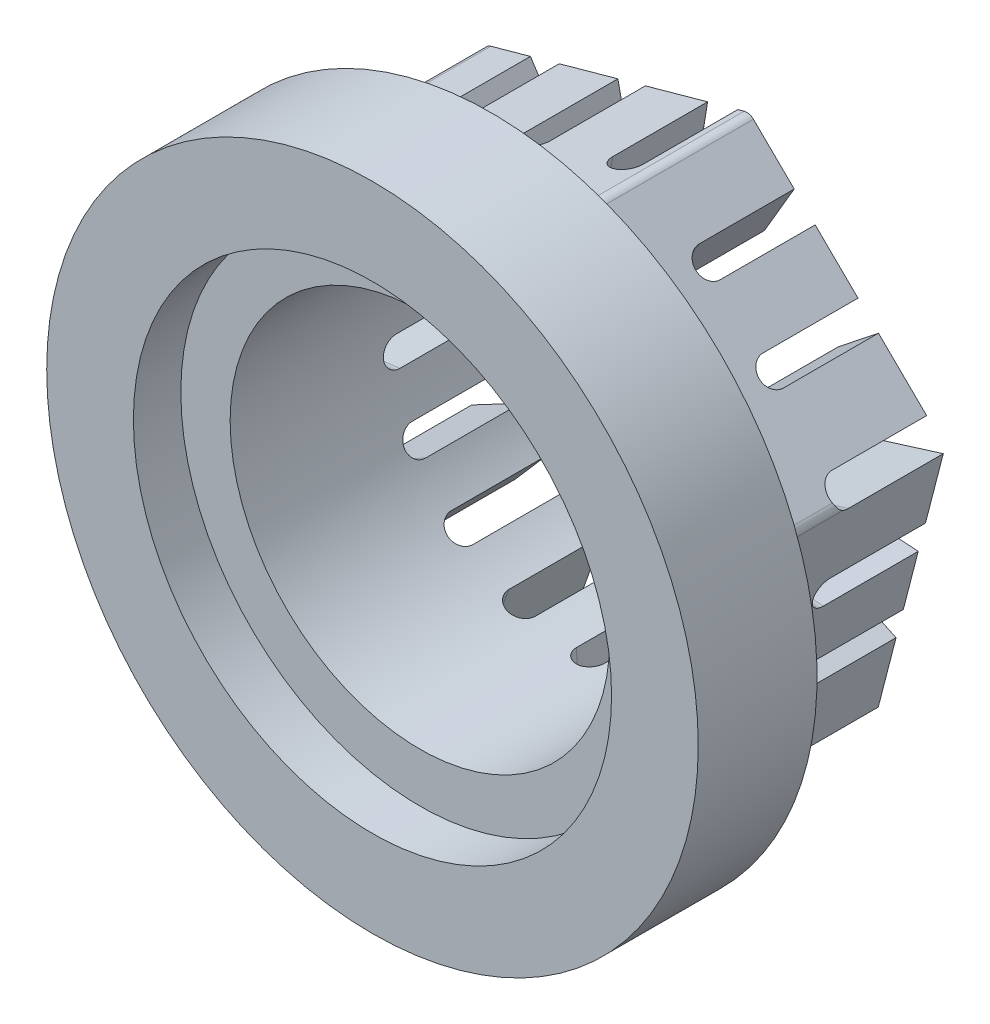
SolidWorks part; units mm, degrees
material "AISI Type 316L stainless steel"
ref_plane "Front Plane" through (0, 0, 0) normal (0, 0, 1) x (1, 0, 0)
ref_plane "Top Plane" through (0, 0, 0) normal (0, 1, 0) x (1, 0, 0)
ref_plane "Right Plane" through (0, 0, 0) normal (1, 0, 0) x (0, 0, -1)
sketch "Sketch1" plane through (0, 0, 0) normal (0, 0, 1) x (1, 0, 0)
  circle A0 centre (0, 0) radius 21.7995
  dimension "D1" = 43.5991
extrude "Boss-Extrude1" add sketch "Sketch1" along normal blind 20.6502
sketch "Sketch2" plane through (0, 0, 20.6502) normal (0, 0, 1) x (1, 0, 0)
  circle A0 centre (0, 0) radius 12.7
  dimension "D1" = 25.4
extrude "Cut-Extrude1" cut sketch "Sketch2" against normal blind 20.6502
sketch "Sketch3" plane through (0, 0, 20.6502) normal (0, 0, 1) x (1, 0, 0)
  circle A0 centre (0, 0) radius 16
  dimension "D1" = 32
extrude "Cut-Extrude2" cut sketch "Sketch3" against normal blind 3.175
sketch "Sketch4" plane through (0, 0, 0) normal (0, 0, -1) x (-1, 0, 0)
  line L1 (17.6618, -4.9073) -> (13.0808, 12.8419)
  line L2 (13.0808, 12.8419) -> (-4.581, 17.7492)
  line L3 (-4.581, 17.7492) -> (-17.6618, 4.9073)
  line L4 (-17.6618, 4.9073) -> (-13.0808, -12.8419)
  line L5 (-13.0808, -12.8419) -> (4.581, -17.7492)
  line L6 (4.581, -17.7492) -> (17.6618, -4.9073)
  circle A1 centre (0, 0) radius 15.875 construction
  dimension "D1" = 31.75
extrude "Cut-Extrude3" cut sketch "Sketch4" against normal blind 12.7 flip side to cut
sketch "Sketch5" plane through (-15.3713, 3.9673, 0) normal (-0.9683, 0.2499, 0) x (0, 0, 1)
  line L0 (0, 0) -> (12.7, 0) construction
  line L1 (12.7, -9.1654) -> (12.7, 9.1654) construction
  line L2 (6.35, 0.9525) -> (0, 0.9525)
  line L3 (0, -9.1654) -> (0, 9.1654) construction
  line L4 (0, 0.9525) -> (0, -0.9525)
  line L5 (0, -0.9525) -> (6.35, -0.9525)
  arc A1 (6.35, 0.9525) -> (6.35, -0.9525) centre (6.35, 0) cw
extrude "Cut-Extrude4" cut sketch "Sketch5" against normal blind 9.8552 and the other way blind 9.8552
pattern_circular "CirPattern1" count 17 over 360 about axis through (0, 0, 17.4752) along (0, 0, 1) of "Cut-Extrude4" reverse direction yes
fillet "Fillet1" radius 0.635 6 edges at (-17.6618, -4.9073, 6.35) (-13.0808, 12.8419, 6.35) (4.581, 17.7492, 6.35) (17.6618, 4.9073, 9.9086) (13.0808, -12.8419, 9.9086) (-4.581, -17.7492, 6.35)
ref_axis "Axis1" through (0, 0, 17.4752) along (0, 0, 1)
